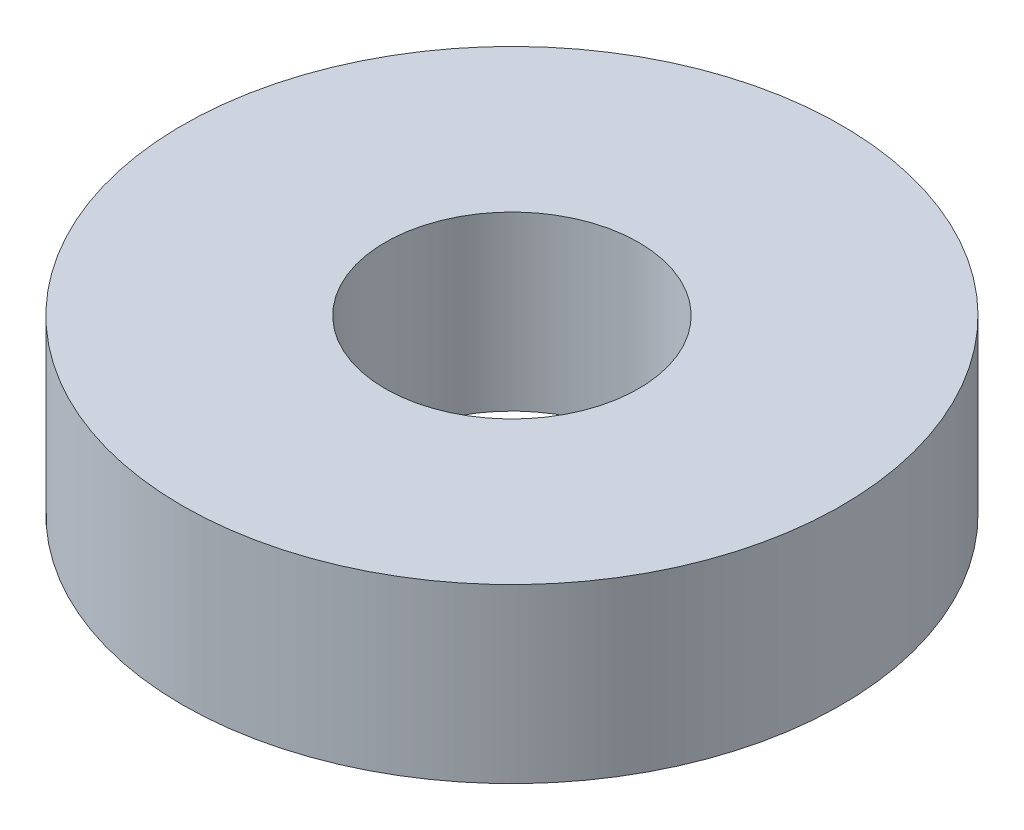
SolidWorks part; units mm, degrees
ref_plane "Front Plane" through (0, 0, 0) normal (0, 0, 1) x (1, 0, 0)
ref_plane "Top Plane" through (0, 0, 0) normal (0, 1, 0) x (1, 0, 0)
ref_plane "Right Plane" through (0, 0, 0) normal (1, 0, 0) x (0, 0, -1)
sketch "Sketch1" plane through (0, 0, 0) normal (0, 1, 0) x (1, 0, 0)
  circle A0 centre (0, 0) radius 32.5
  dimension "FLANGE_OD" = 65
extrude "Boss-Extrude1" add sketch "Sketch1" along normal blind 17
sketch "Sketch2" plane through (0, 0, 0) normal (0, 1, 0) x (1, 0, 0)
  circle A0 centre (0, 0) radius 12.5
  dimension "BORE_D" = 25
extrude "Cut-Extrude1" cut sketch "Sketch2" along normal through all
sketch "Sketch3" plane through (0, 17, 0) normal (0, 1, 0) x (1, 0, 0)
  circle A0 centre (0, 0) radius 8.1676 construction
  circle A1 centre (-8.1676, 0) radius 2.2441
  dimension "BOLT_D" = 4.4882
  dimension "BOLT_PCD" = 16.3353
extrude "Cut-Extrude2" cut sketch "Sketch3" against normal blind 14.7481 rebuild error yes
pattern_circular "CirPattern1" count 5 over 360 rebuild error yes
